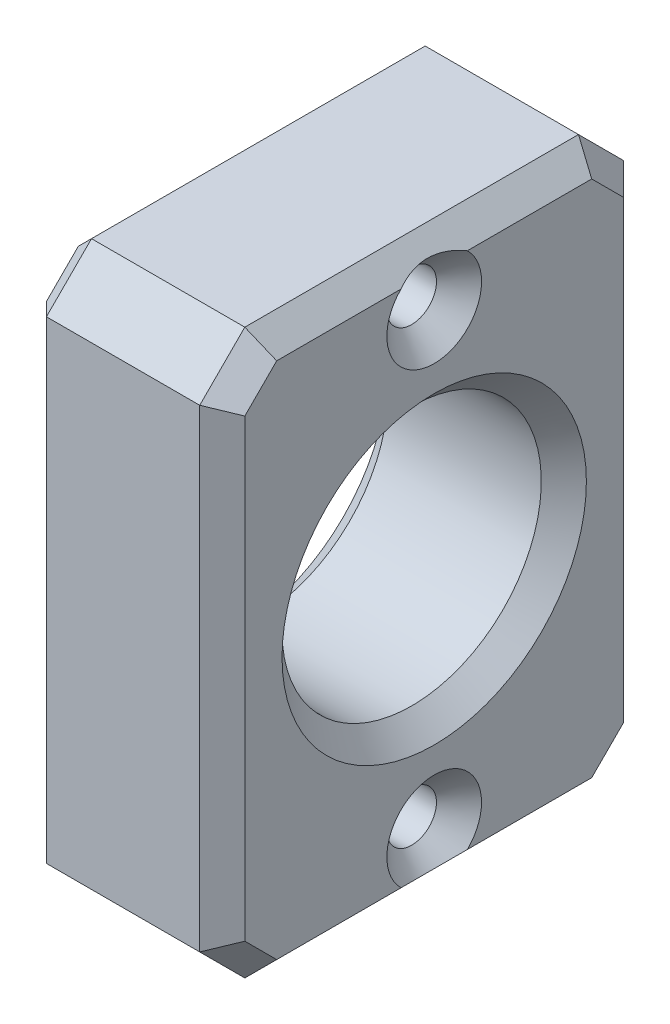
SolidWorks part; units mm, degrees
ref_plane "Front Plane" through (0, 0, 0) normal (0, 0, 1) x (1, 0, 0)
ref_plane "Top Plane" through (0, 0, 0) normal (0, 1, 0) x (1, 0, 0)
ref_plane "Right Plane" through (0, 0, 0) normal (1, 0, 0) x (0, 0, -1)
sketch "Sketch1" plane through (0, 0, 0) normal (1, 0, 0) x (0, 0, -1)
  line L0 (0, 25.4) -> (0, -25.4) construction
  line L1 (-23.876, -31.75) -> (23.876, -31.75)
  line L2 (-23.876, -31.75) -> (-23.876, 31.75)
  line L3 (-23.876, 31.75) -> (23.876, 31.75)
  line L4 (23.876, -31.75) -> (23.876, 31.75)
  line L5 (-23.876, -31.75) -> (23.876, 31.75) construction
  line L6 (-23.876, 31.75) -> (23.876, -31.75) construction
  circle A0 centre (0, 0) radius 14.605
  circle A1 centre (0, -25.4) radius 2.794
  circle A2 centre (0, 25.4) radius 2.794
  point P0 (0, 0)
  dimension "D3" = 29.21
  dimension "D5" = 5.588
  dimension "D1" = 47.752
  dimension "D2" = 63.5
  dimension "D4" = 50.8
extrude "Boss-Extrude1" add sketch "Sketch1" along normal mid plane 22.352
fillet "Fillet1" radius 5.08 4 edges at (0, 31.75, -23.876) (0, 31.75, 23.876) (0, -31.75, 23.876) (0, -31.75, -23.876) profile chamfer
chamfer "Chamfer1" distance 2.54 angle 45 22 edges at (-11.176, 25.4, -2.794) (-11.176, 0, -14.605) (-11.176, 29.21, 21.336) (-11.176, 0, 23.876) (-11.176, -29.21, 21.336) (-11.176, -31.75, 0) (-11.176, -29.21, -21.336) (-11.176, 0, -23.876) (-11.176, 29.21, -21.336) (-11.176, 31.75, 0) (-11.176, -25.4, -2.794) (11.176, 25.4, -2.794) (11.176, -25.4, -2.794) (11.176, 0, -14.605) (11.176, -29.21, -21.336) (11.176, -31.75, 0) (11.176, -29.21, 21.336) (11.176, 0, 23.876) (11.176, 29.21, 21.336) (11.176, 31.75, 0) (11.176, 29.21, -21.336) (11.176, 0, -23.876)
equation "\"Print_Tolerance_ID\"= 0.02"
equation "\"D5@Sketch1\"=0.2+\"Print_Tolerance_ID\""
equation "\"D3@Sketch1\"=1.13in+\"Print_Tolerance_ID\""
equation "\"D1@Sketch1\"=1.88"
